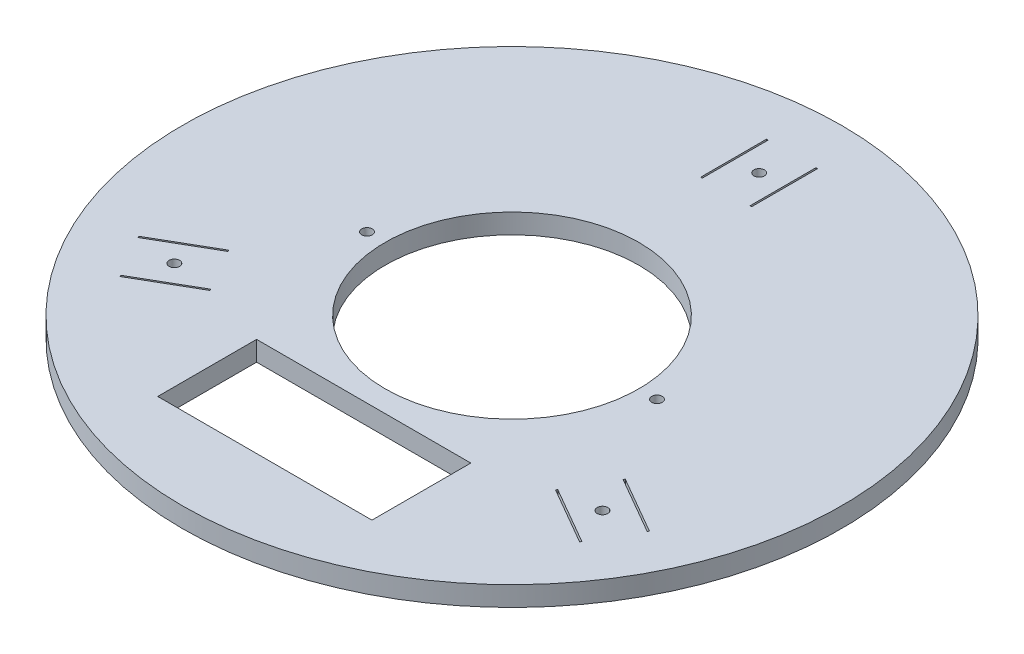
SolidWorks part; units mm, degrees
ref_plane "Front Plane" through (0, 0, 0) normal (0, 0, 1) x (1, 0, 0)
ref_plane "Top Plane" through (0, 0, 0) normal (0, 1, 0) x (1, 0, 0)
ref_plane "Right Plane" through (0, 0, 0) normal (1, 0, 0) x (0, 0, -1)
sketch "Sketch2" plane through (0, 0, 0) normal (0, 1, 0) x (1, 0, 0)
  circle A0 centre (0, 0) radius 100
  dimension "D1" = 200
extrude "Boss-Extrude1" add sketch "Sketch2" along normal blind 6
sketch "Sketch3" plane through (0, 6, 0) normal (0, 1, 0) x (1, 0, 0)
  line L0 (0, 0) -> (0, 100) construction
  line L1 (-7.5, 75) -> (7.5, 75) construction
  line L3 (-7.75, 65) -> (-7.25, 65)
  line L4 (-7.75, 65) -> (-7.75, 85)
  line L5 (-7.75, 85) -> (-7.25, 85)
  line L6 (-7.25, 65) -> (-7.25, 85)
  line L7 (-7.75, 65) -> (-7.25, 85) construction
  line L8 (-7.75, 85) -> (-7.25, 65) construction
  line L9 (7.25, 65) -> (7.75, 65)
  line L10 (7.25, 65) -> (7.25, 85)
  line L11 (7.25, 85) -> (7.75, 85)
  line L12 (7.75, 65) -> (7.75, 85)
  line L13 (7.25, 65) -> (7.75, 85) construction
  line L14 (7.25, 85) -> (7.75, 65) construction
  line L30 (60.1667, -25.7883) -> (77.4872, -35.7883)
  line L31 (60.1667, -25.7883) -> (59.9167, -26.2213)
  line L32 (59.9167, -26.2213) -> (77.2372, -36.2213)
  line L33 (77.4872, -35.7883) -> (77.2372, -36.2213)
  line L34 (52.6667, -38.7787) -> (69.9872, -48.7787)
  line L35 (52.6667, -38.7787) -> (52.4167, -39.2117)
  line L36 (52.4167, -39.2117) -> (69.7372, -49.2117)
  line L37 (69.9872, -48.7787) -> (69.7372, -49.2117)
  line L38 (-52.4167, -39.2117) -> (-69.7372, -49.2117)
  line L39 (-52.4167, -39.2117) -> (-52.6667, -38.7787)
  line L40 (-52.6667, -38.7787) -> (-69.9872, -48.7787)
  line L41 (-69.7372, -49.2117) -> (-69.9872, -48.7787)
  line L42 (-59.9167, -26.2213) -> (-77.2372, -36.2213)
  line L43 (-59.9167, -26.2213) -> (-60.1667, -25.7883)
  line L44 (-60.1667, -25.7883) -> (-77.4872, -35.7883)
  line L45 (-77.2372, -36.2213) -> (-77.4872, -35.7883)
  circle A0 centre (0, 0) radius 100 construction
  circle A1 centre (0, 75) radius 1.6
  circle A2 centre (64.9519, -37.5) radius 1.6
  circle A3 centre (-64.9519, -37.5) radius 1.6
  point P8 (0, 75)
  point P19 (0, 0)
  point P36 (0, 0)
  point P37 (0, 0)
  point P44 (0, 0)
  dimension "D6" = 3.2
  dimension "D1" = 15
  dimension "D2" = 20
  dimension "D3" = 0.5
  dimension "D4" = 75
  dimension "D5" = 3
  dimension "D7" = 3
extrude "Cut-Extrude1" cut sketch "Sketch3" against normal through all
sketch "Sketch4" plane through (0, 6, 0) normal (0, 1, 0) x (1, 0, 0)
  circle A0 centre (0, 0) radius 38.5
  dimension "D1" = 77
extrude "Cut-Extrude2" cut sketch "Sketch4" against normal through all
sketch "Sketch5" plane through (0, 6, 0) normal (0, 1, 0) x (1, 0, 0)
  line L0 (0, 0) -> (50000, 0) construction
  line L1 (0, 0) -> (0, 50000) construction
  circle A0 centre (-44, 0) radius 1.6
  circle A1 centre (44, 0) radius 1.6
  dimension "D2" = 3.2
  dimension "D1" = 44
extrude "Cut-Extrude3" cut sketch "Sketch5" against normal through all
sketch "Sketch6" plane through (0, 6, 0) normal (0, 1, 0) x (1, 0, 0)
  line L1 (-32.5, -45) -> (32.5, -45)
  line L2 (-32.5, -45) -> (-32.5, -75)
  line L3 (-32.5, -75) -> (32.5, -75)
  line L4 (32.5, -45) -> (32.5, -75)
  point P4 (0, -45)
  dimension "D1" = 45
  dimension "D2" = 30
  dimension "D3" = 65
extrude "Cut-Extrude4" cut sketch "Sketch6" against normal through all
equation "\"Leg_Spacing\"=15"
equation "\"D1@Sketch3\"=\"Leg_Spacing\""
equation "\"Leaf_Spring_Slot_Width\"=20"
equation "\"D2@Sketch3\"=\"Leaf_Spring_Slot_Width\""
equation "\"Leaf_Spring_Thickness\"=0.5"
equation "\"D3@Sketch3\"=\"Leaf_Spring_Thickness\""
equation "\"Inner_Radius\"=75"
equation "\"D4@Sketch3\"=\"Inner_Radius\""
equation "\"Camera\"=77"
equation "\"D1@Sketch4\"=\"Camera\""
